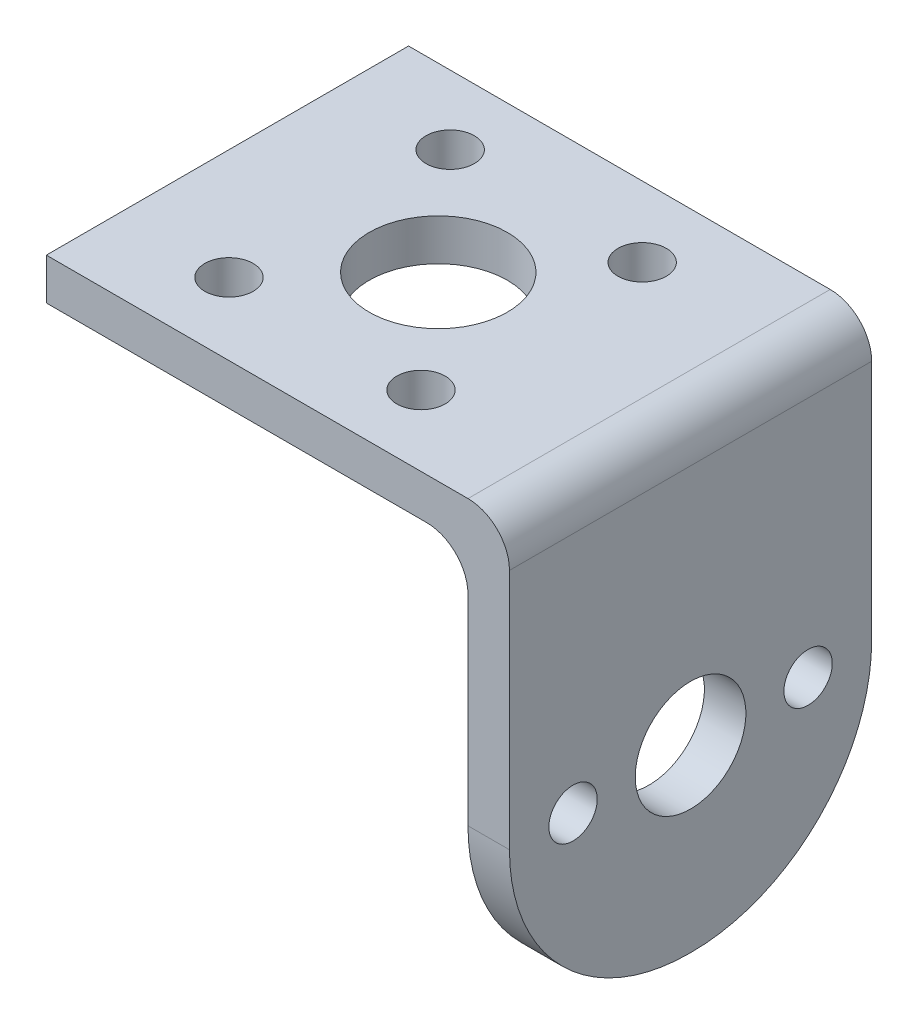
SolidWorks part; units mm, degrees
ref_plane "Front Plane" through (0, 0, 0) normal (0, 0, 1) x (1, 0, 0)
ref_plane "Top Plane" through (0, 0, 0) normal (0, 1, 0) x (1, 0, 0)
ref_plane "Right Plane" through (0, 0, 0) normal (1, 0, 0) x (0, 0, -1)
sketch "Sketch1" plane through (0, 0, 0) normal (0, 1, 0) x (1, 0, 0)
  line L1 (0, 0) -> (33.5, 0)
  line L2 (0, 0) -> (0, 26.2)
  line L3 (0, 26.2) -> (33.5, 26.2)
  line L4 (33.5, 0) -> (33.5, 26.2)
  dimension "D1" = 33.5
  dimension "D2" = 26.2
extrude "Boss-Extrude1" add sketch "Sketch1" along normal blind 3
sketch "Sketch3" plane through (0, 0, 0) normal (0, -1, 0) x (1, 0, 0)
  line L1 (33.5, -26.2) -> (0, -26.2) construction
  line L2 (33.5, 0) -> (30.5, 0)
  line L3 (33.5, 0) -> (33.5, -26.2)
  line L4 (33.5, -26.2) -> (30.5, -26.2)
  line L5 (30.5, 0) -> (30.5, -26.2)
  dimension "D1" = 3
extrude "Boss-Extrude3" add sketch "Sketch3" along normal blind 30.5
fillet "Fillet1" radius 13 2 edges at (32, -30.5, 0) (32, -30.5, -26.2)
sketch "Sketch7" plane through (0, 0, 0) normal (0, -1, 0) x (1, 0, 0)
  line L0 (8, 0) -> (8, -26.2)
  line L1 (0, 0) -> (30.5, 0)
  line L2 (0, 0) -> (0, -26.2)
  line L3 (0, -26.2) -> (30.5, -26.2)
  line L4 (30.5, 0) -> (30.5, -26.2)
  line L5 (8, -5.2113) -> (8, -21.2113)
  line L6 (22, 0) -> (22, -26.2)
  line L7 (0, -13.1) -> (30.5, -13.1)
  circle A2 centre (8, -13.1) radius 8
  circle A3 centre (8, -5.2113) radius 1.75
  circle A4 centre (8, -21.2113) radius 1.75
  circle A5 centre (22, -13.1) radius 8
  circle A6 centre (22, -21.1) radius 1.75
  circle A7 centre (22, -5.1) radius 1.75
  circle A8 centre (15.25, -13.1) radius 5
  dimension "D2" = 16
  dimension "D3" = 3.5
  dimension "D5" = 14
  dimension "D4" = 3.5
  dimension "D6" = 16
  dimension "D7" = 3.5
  dimension "D8" = 3.5
  dimension "D9" = 10
  dimension "D1" = 8
extrude "Cut-Extrude1" cut sketch "Sketch7" against normal through all contours A4 | A3 | A6 | A7 | A8
fillet "Fillet2" radius 3 2 edges at (30.5, 0, -13.1) (33.5, 3, -13.1)
sketch "Sketch10" plane through (33.5, 0, 0) normal (1, 0, 0) x (0, 0, -1)
  line L2 (13.2, -17.5) -> (26.2, -17.5)
  line L3 (13.2, -17.5) -> (13, -17.5)
  line L4 (13.2, -17.5) -> (13, -17.5)
  line L5 (13, -17.5) -> (0, -17.5)
  circle A0 centre (13.1, -17.5) radius 8.5
  circle A1 centre (4.6, -17.5) radius 3
  circle A2 centre (21.6, -17.5) radius 3
  circle A3 centre (4.6, -17.5) radius 1.75
  circle A4 centre (21.6, -17.5) radius 1.75
  circle A5 centre (13.1, -17.5) radius 4
  dimension "D2" = 17
  dimension "D3" = 3.5
  dimension "D4" = 3.5
  dimension "D5" = 6
  dimension "D6" = 6
  dimension "D7" = 8
  dimension "D1" = 13
extrude "Cut-Extrude2" cut sketch "Sketch10" against normal blind 3.5 and the other way through all contours A4 | A3 | A5
